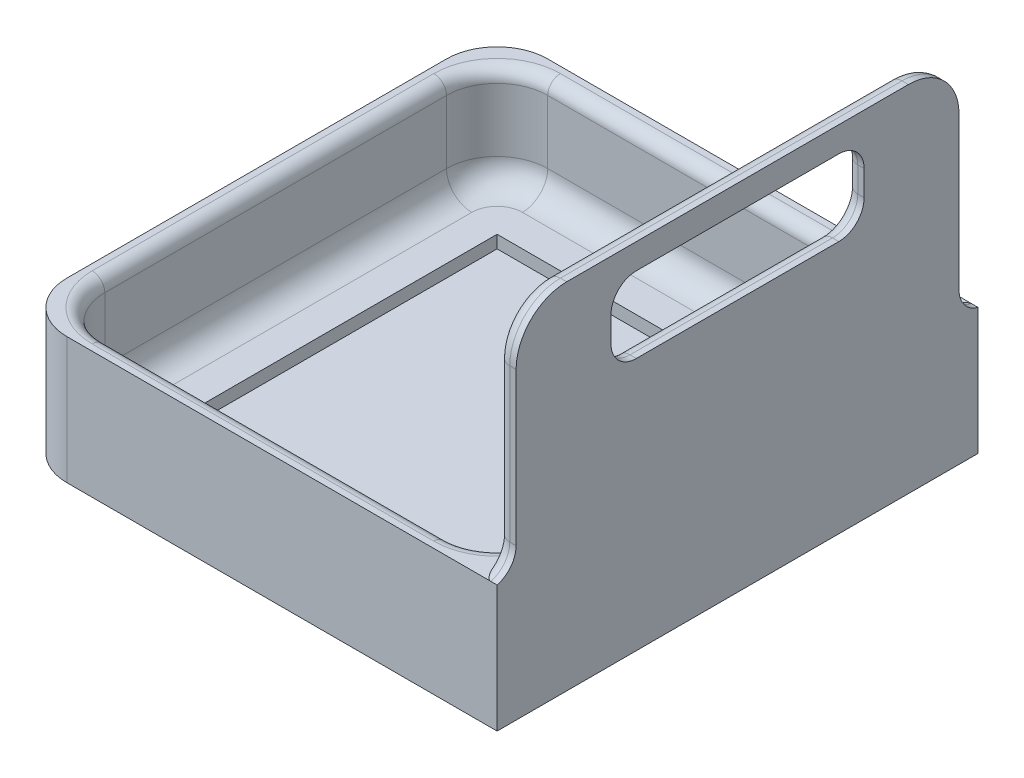
SolidWorks part; units mm, degrees
ref_plane "Front Plane" through (0, 0, 0) normal (0, 0, 1) x (1, 0, 0)
ref_plane "Top Plane" through (0, 0, 0) normal (0, 1, 0) x (1, 0, 0)
ref_plane "Right Plane" through (0, 0, 0) normal (1, 0, 0) x (0, 0, -1)
sketch "Sketch1" plane through (0, 0, 0) normal (0, 1, 0) x (1, 0, 0)
  line L1 (-95, -95) -> (95, -95)
  line L2 (-95, -95) -> (-95, 95)
  line L3 (-95, 95) -> (95, 95)
  line L4 (95, -95) -> (95, 95)
  line L5 (-95, -95) -> (95, 95) construction
  line L6 (-95, 95) -> (95, -95) construction
  point P0 (0, 0)
  dimension "D1" = 190
  dimension "D2" = 190
extrude "Boss-Extrude1" add sketch "Sketch1" along normal blind 10
sketch "Sketch2" plane through (0, 10, 0) normal (0, 1, 0) x (1, 0, 0)
  line L0 (-95, -95) -> (95, -95) construction
  line L1 (-95, 95) -> (-95, -95) construction
  line L2 (95, -95) -> (95, 95) construction
  line L3 (95, 95) -> (-95, 95) construction
  line L4 (-95, -95) -> (95, -95)
  line L5 (-95, 95) -> (-95, -95)
  line L6 (95, -95) -> (95, 95)
  line L7 (95, 95) -> (-95, 95)
  line L9 (-87.5, -87.5) -> (87.5, -87.5)
  line L10 (-87.5, -87.5) -> (-87.5, 87.5)
  line L11 (-87.5, 87.5) -> (87.5, 87.5)
  line L12 (87.5, -87.5) -> (87.5, 87.5)
  line L13 (-87.5, -87.5) -> (87.5, 87.5) construction
  line L14 (-87.5, 87.5) -> (87.5, -87.5) construction
  point P3 (0, 0)
  dimension "D1" = 175
  dimension "D2" = 175
extrude "Boss-Extrude2" add sketch "Sketch2" along normal blind 40
sketch "Sketch3" plane through (0, 50, 0) normal (0, 1, 0) x (1, 0, 0)
  line L0 (87.5, 87.5) -> (95, 87.5)
  line L1 (95, -95) -> (95, 95) construction
  line L2 (87.5, -87.5) -> (87.5, 87.5) construction
  line L3 (95, -87.5) -> (95, 87.5)
  line L4 (87.5, -87.5) -> (87.5, 87.5)
  line L5 (87.5, -87.5) -> (95, -87.5)
extrude "Boss-Extrude3" add sketch "Sketch3" along normal blind 90
sketch "Sketch4" plane through (87.5, 0, 0) normal (-1, 0, 0) x (0, 0, 1)
  line L0 (-87.5, 140) -> (87.5, 140) construction
  line L1 (-50, 100) -> (50, 100)
  line L2 (-50, 100) -> (-50, 130)
  line L3 (-50, 130) -> (50, 130)
  line L4 (50, 100) -> (50, 130)
  line L5 (-50, 100) -> (50, 130) construction
  line L6 (-50, 130) -> (50, 100) construction
  point P0 (0, 115)
  point P5 (0, 0)
  dimension "D1" = 100
  dimension "D2" = 30
  dimension "D3" = 10
extrude "Cut-Extrude1" cut sketch "Sketch4" against normal through all
fillet "Fillet2" radius 20 8 edges at (91.25, 140, -87.5) (91.25, 140, 87.5) (87.5, 30, 87.5) (87.5, 30, -87.5) (-87.5, 30, 87.5) (-87.5, 30, -87.5) (-95, 25, -95) (-95, 25, 95)
fillet "Fillet3" radius 10 14 edges at (81.6421, 10, 81.6421) (0, 10, 87.5) (-81.6421, 10, 81.6421) (-87.5, 10, 0) (-81.6421, 10, -81.6421) (0, 10, -87.5) (81.6421, 10, -81.6421) (87.5, 10, 0) (91.25, 50, -87.5) (91.25, 50, 87.5) (91.25, 130, 50) (91.25, 100, 50) (91.25, 130, -50) (91.25, 100, -50)
fillet "Fillet4" radius 5 22 edges at (81.6421, 50, -81.6421) (0, 50, -87.5) (-81.6421, 50, -81.6421) (-87.5, 50, 0) (-81.6421, 50, 81.6421) (81.6421, 50, 81.6421) (87.5, 102.9289, -47.0711) (87.5, 115, -50) (87.5, 127.0711, -47.0711) (87.5, 130, 0) (87.5, 127.0711, 47.0711) (87.5, 115, 50) (87.5, 102.9289, 47.0711) (0, 50, 87.5) (87.5, 100, 0) (87.5, 53.5587, -89.5943) (87.5, 89.8412, -87.5) (87.5, 134.1421, -81.6421) (87.5, 53.5587, 89.5943) (87.5, 89.8412, 87.5) (87.5, 134.1421, 81.6421) (87.5, 140, 0)
sketch "Sketch6" plane through (0, 10, 0) normal (0, 1, 0) x (1, 0, 0)
  line L1 (-65, -65) -> (65, -65)
  line L2 (-65, -65) -> (-65, 65)
  line L3 (-65, 65) -> (65, 65)
  line L4 (65, -65) -> (65, 65)
  line L5 (-65, -65) -> (65, 65) construction
  line L6 (-65, 65) -> (65, -65) construction
  point P0 (0, 0)
  dimension "D1" = 130
extrude "Cut-Extrude3" cut sketch "Sketch6" against normal blind 5
